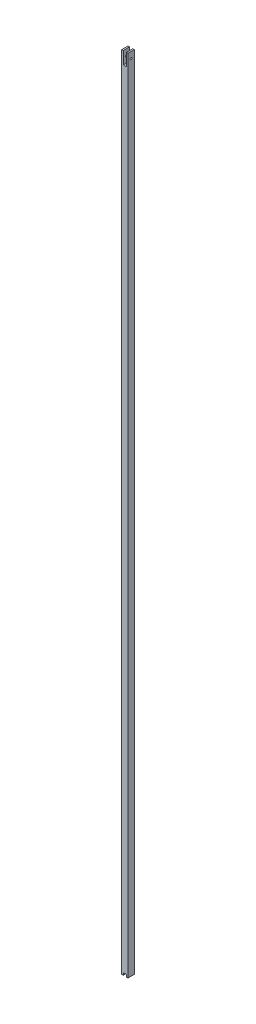
SolidWorks part; units mm, degrees
material "Plain Carbon Steel"
ref_plane "Front Plane" through (0, 0, 0) normal (0, 0, 1) x (1, 0, 0)
ref_plane "Top Plane" through (0, 0, 0) normal (0, 1, 0) x (1, 0, 0)
ref_plane "Right Plane" through (0, 0, 0) normal (1, 0, 0) x (0, 0, -1)
sketch "Sketch1" plane through (0, 0, 0) normal (0, 0, 1) x (1, 0, 0)
  line L0 (0, 0) -> (1.5875, 0)
  line L1 (1.5875, 0) -> (1.5875, 2.3812)
  line L2 (1.5875, 2.3812) -> (4.7625, 2.3812)
  line L3 (4.7625, 2.3812) -> (4.7625, 0)
  line L4 (4.7625, 0) -> (6.35, 0)
  line L5 (6.35, 0) -> (6.35, 812.8)
  line L6 (6.35, 812.8) -> (4.7625, 812.8)
  line L7 (4.7625, 812.8) -> (4.7625, 800.1)
  line L8 (4.7625, 800.1) -> (1.5875, 800.1)
  line L9 (1.5875, 800.1) -> (1.5875, 812.8)
  line L10 (1.5875, 812.8) -> (0, 812.8)
  line L11 (0, 812.8) -> (0, 0)
  dimension "D1" = 1.5875
  dimension "D2" = 2.3812
  dimension "D3" = 3.175
  dimension "D4" = 2.3812
  dimension "D5" = 1.5875
  dimension "D6" = 812.8
  dimension "D7" = 1.5875
  dimension "D8" = 12.7
  dimension "D9" = 3.175
  dimension "D10" = 12.7
extrude "Boss-Extrude1" add sketch "Sketch1" along normal blind 6.35
sketch "Sketch2" plane through (0, 0, 0) normal (1, 0, 0) x (0, 0, -1)
  circle A0 centre (3.175, 806.45) radius 1
  dimension "D3" = 2
  dimension "D1" = 3.175
  dimension "D2" = 806.45
sketch "Sketch3" plane through (0, 0, 0) normal (1, 0, 0) x (0, 0, -1)
  circle A0 centre (-3.175, 806.45) radius 1
  dimension "D3" = 2
  dimension "D1" = 3.175
  dimension "D2" = 806.45
extrude "Cut-Extrude3" cut sketch "Sketch3" against normal mid plane 20
